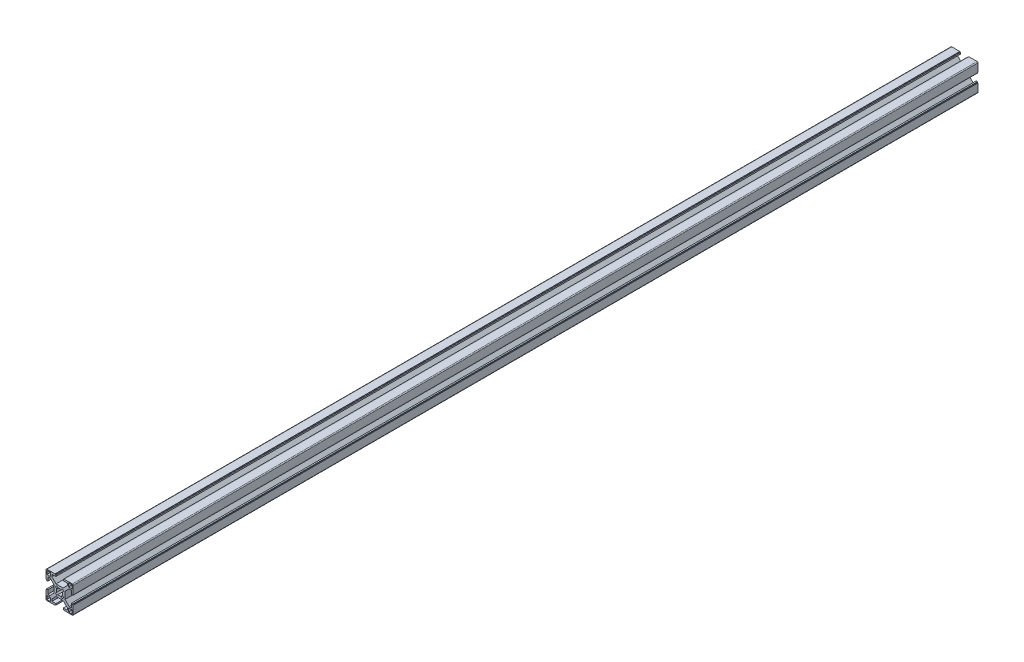
SolidWorks part; units mm, degrees
ref_plane "Plano frontal" through (0, 0, 0) normal (0, 0, 1) x (1, 0, 0)
ref_plane "Plano superior" through (0, 0, 0) normal (0, 1, 0) x (1, 0, 0)
ref_plane "Plano direito" through (0, 0, 0) normal (1, 0, 0) x (0, 0, -1)
sketch "Esboço1" plane through (0, 0, 0) normal (0, 0, 1) x (1, 0, 0)
  line L5 (0, 0) -> (-17.7944, 17.7944) construction
  line L6 (0, 3.5) -> (0, 6)
  line L8 (0, 6) -> (-3.8787, 6)
  line L9 (-3.5, 0) -> (-6, 0)
  line L48 (-6, 0) -> (-6, 3.8787)
  line L49 (-3.8787, 6) -> (-8.5, 10.6213)
  line L50 (-6, 3.8787) -> (-10.6213, 8.5)
  line L51 (0, 0) -> (-12.921, 0) construction
  line L52 (-8.5, 13) -> (-4.1, 13)
  line L53 (-4.1, 13) -> (-4.1, 14.5)
  line L54 (-4.1, 14.5) -> (-5.1, 14.5)
  line L55 (-5.1, 14.5) -> (-5.1, 15)
  line L56 (-5.1, 15) -> (-15, 15)
  line L57 (-15, 5.1) -> (-15, 15)
  line L58 (-14.5, 5.1) -> (-15, 5.1)
  line L59 (-14.5, 4.1) -> (-14.5, 5.1)
  line L60 (-13, 4.1) -> (-14.5, 4.1)
  line L61 (-13, 8.5) -> (-13, 4.1)
  line L62 (-1.6646, 3.0788) -> (-3.182, 4.5962)
  line L63 (-3.0788, 1.6646) -> (-4.5962, 3.182)
  line L64 (-4.5962, 3.182) -> (-3.182, 4.5962)
  line L65 (-8.5, 13) -> (-8.5, 10.6213)
  line L66 (-10, 14) -> (-14, 14)
  line L67 (-10, 14) -> (-10, 10)
  line L68 (-10, 10) -> (-14, 10)
  line L69 (-14, 14) -> (-14, 10)
  line L70 (-10, 14) -> (-14, 10) construction
  line L71 (-10, 10) -> (-14, 14) construction
  line L72 (-13, 8.5) -> (-10.6213, 8.5)
  circle A1 centre (0, 0) radius 3.5
  point P25 (-12, 12)
  dimension "D5" = 10.9
  dimension "D9" = 5.5
  dimension "D10" = 2
  dimension "D11" = 4
  dimension "D12" = 4
  dimension "D13" = 1
  dimension "D1" = 7
  dimension "D2" = 6
  dimension "D3" = 3
  dimension "D4" = 9.9
  dimension "D6" = 0.5
  dimension "D7" = 1.5
  dimension "D8" = 15
  dimension "D14" = 6.5
extrude "Ressalto-extrusão1" add sketch "Esboço1" along normal blind 1000 contours A1 L6 L8 L49 L65 L52 L53 L54 L55 L56 L57 L58 L59 L60 L61 L72 L50 L48 L9 L63 L64 L62 L69 L66 L67 L68 region at (-8.2712, 8.2712, 0)
sketch "Esboço3" plane through (0, 0, 0) normal (1, 0, 0) x (0, 0, -1)
  line L0 (0, 0) -> (-1000, 0) construction
  dimension "D1" = 1000
pattern_circular "PadrãoCircular1" count 4 every 90 about axis through (0, 0, 0) along (0, 0, 1) of "Ressalto-extrusão1"
fillet "Filete1" radius 1 4 edges at (15, 15, 500) (-15, 15, 500) (-15, -15, 500) (15, -15, 500)
